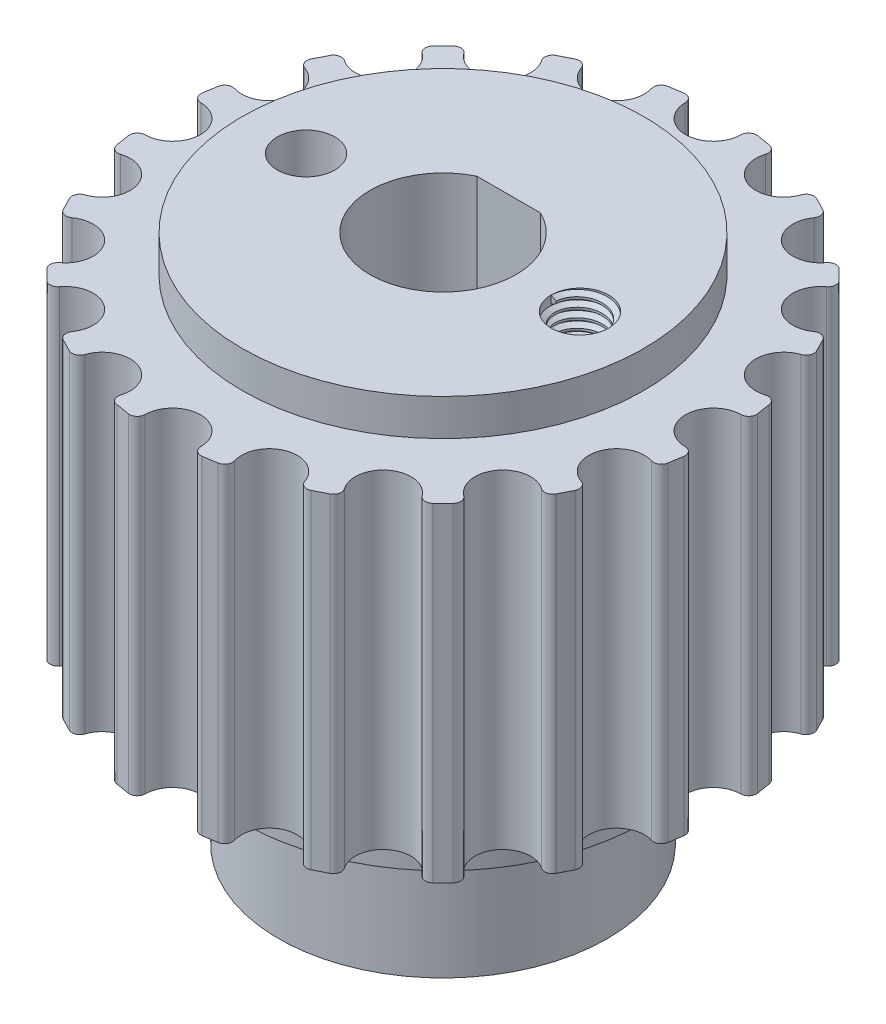
SolidWorks part; units mm, degrees
ref_plane "Ebene vorne" through (0, 0, 0) normal (0, 0, 1) x (1, 0, 0)
ref_plane "Ebene oben" through (0, 0, 0) normal (0, 1, 0) x (1, 0, 0)
ref_plane "Ebene rechts" through (0, 0, 0) normal (1, 0, 0) x (0, 0, -1)
sketch "Skizze1" plane through (0, 0, 0) normal (0, 1, 0) x (1, 0, 0)
  line L0 (0, 0) -> (0, 12990.3785) construction
  line L1 (0, 0) -> (-12990.3785, 0) construction
  line L2 (0, 0) -> (7.951, 24.4706) construction
  line L3 (2.7773, 15.0914) -> (2.0221, 15.211)
  line L4 (7.3049, 13.4946) -> (6.6236, 13.8417)
  line L5 (11.1174, 10.5768) -> (10.5768, 11.1174)
  line L6 (13.8417, 6.6236) -> (13.4946, 7.3049)
  line L7 (15.211, 2.0221) -> (15.0914, 2.7773)
  line L8 (15.0914, -2.7773) -> (15.211, -2.0221)
  line L9 (13.4946, -7.3049) -> (13.8417, -6.6236)
  line L10 (10.5768, -11.1174) -> (11.1174, -10.5768)
  line L11 (6.6236, -13.8417) -> (7.3049, -13.4946)
  line L12 (2.0221, -15.211) -> (2.7773, -15.0914)
  line L13 (-2.7773, -15.0914) -> (-2.0221, -15.211)
  line L14 (-7.3049, -13.4946) -> (-6.6236, -13.8417)
  line L15 (-11.1174, -10.5768) -> (-10.5768, -11.1174)
  line L16 (-13.8417, -6.6236) -> (-13.4946, -7.3049)
  line L17 (-15.211, -2.0221) -> (-15.0914, -2.7773)
  line L18 (-15.0914, 2.7773) -> (-15.211, 2.0221)
  line L19 (-13.4946, 7.3049) -> (-13.8417, 6.6236)
  line L20 (-10.5768, 11.1174) -> (-11.1174, 10.5768)
  line L21 (-6.6236, 13.8417) -> (-7.3049, 13.4946)
  line L22 (-2.0221, 15.211) -> (-2.7773, 15.0914)
  circle A0 centre (0, 0) radius 15.345 construction
  circle A1 centre (0, 0) radius 13.285 construction
  arc A2 (0, 13.285) -> (1.5249, 14.7915) centre (0, 14.81) ccw
  arc A3 (2.0221, 15.211) -> (1.5249, 14.7915) centre (1.9549, 14.7863) ccw
  arc A4 (3.1206, 14.5388) -> (4.1053, 12.6348) centre (4.5765, 14.0851) ccw
  arc A5 (3.1206, 14.5388) -> (2.7773, 15.0914) centre (2.7101, 14.6667) ccw
  arc A6 (4.1053, 12.6348) -> (6.0211, 13.5964) centre (4.5765, 14.0851) ccw
  arc A7 (6.6236, 13.8417) -> (6.0211, 13.5964) centre (6.4284, 13.4586) ccw
  arc A8 (7.4606, 12.8629) -> (7.3049, 13.4946) centre (7.1097, 13.1114) ccw
  arc A9 (7.4606, 12.8629) -> (7.8087, 10.7478) centre (8.7051, 11.9815) ccw
  arc A10 (7.8087, 10.7478) -> (9.9279, 11.0703) centre (8.7051, 11.9815) ccw
  arc A11 (10.5768, 11.1174) -> (9.9279, 11.0703) centre (10.2727, 10.8134) ccw
  arc A12 (11.0703, 9.9279) -> (11.1174, 10.5768) centre (10.8134, 10.2727) ccw
  arc A13 (11.0703, 9.9279) -> (10.7478, 7.8087) centre (11.9815, 8.7051) ccw
  arc A14 (10.7478, 7.8087) -> (12.8629, 7.4606) centre (11.9815, 8.7051) ccw
  arc A15 (13.4946, 7.3049) -> (12.8629, 7.4606) centre (13.1114, 7.1097) ccw
  arc A16 (13.5964, 6.0211) -> (13.8417, 6.6236) centre (13.4586, 6.4284) ccw
  arc A17 (13.5964, 6.0211) -> (12.6348, 4.1053) centre (14.0851, 4.5765) ccw
  arc A18 (12.6348, 4.1053) -> (14.5388, 3.1206) centre (14.0851, 4.5765) ccw
  arc A19 (15.0914, 2.7773) -> (14.5388, 3.1206) centre (14.6667, 2.7101) ccw
  arc A20 (14.7915, 1.5249) -> (15.211, 2.0221) centre (14.7863, 1.9549) ccw
  arc A21 (14.7915, 1.5249) -> (13.285, 0) centre (14.81, 0) ccw
  arc A22 (13.285, 0) -> (14.7915, -1.5249) centre (14.81, 0) ccw
  arc A23 (15.211, -2.0221) -> (14.7915, -1.5249) centre (14.7863, -1.9549) ccw
  arc A24 (14.5388, -3.1206) -> (15.0914, -2.7773) centre (14.6667, -2.7101) ccw
  arc A25 (14.5388, -3.1206) -> (12.6348, -4.1053) centre (14.0851, -4.5765) ccw
  arc A26 (12.6348, -4.1053) -> (13.5964, -6.0211) centre (14.0851, -4.5765) ccw
  arc A27 (13.8417, -6.6236) -> (13.5964, -6.0211) centre (13.4586, -6.4284) ccw
  arc A28 (12.8629, -7.4606) -> (13.4946, -7.3049) centre (13.1114, -7.1097) ccw
  arc A29 (12.8629, -7.4606) -> (10.7478, -7.8087) centre (11.9815, -8.7051) ccw
  arc A30 (10.7478, -7.8087) -> (11.0703, -9.9279) centre (11.9815, -8.7051) ccw
  arc A31 (11.1174, -10.5768) -> (11.0703, -9.9279) centre (10.8134, -10.2727) ccw
  arc A32 (9.9279, -11.0703) -> (10.5768, -11.1174) centre (10.2727, -10.8134) ccw
  arc A33 (9.9279, -11.0703) -> (7.8087, -10.7478) centre (8.7051, -11.9815) ccw
  arc A34 (7.8087, -10.7478) -> (7.4606, -12.8629) centre (8.7051, -11.9815) ccw
  arc A35 (7.3049, -13.4946) -> (7.4606, -12.8629) centre (7.1097, -13.1114) ccw
  arc A36 (6.0211, -13.5964) -> (6.6236, -13.8417) centre (6.4284, -13.4586) ccw
  arc A37 (6.0211, -13.5964) -> (4.1053, -12.6348) centre (4.5765, -14.0851) ccw
  arc A38 (4.1053, -12.6348) -> (3.1206, -14.5388) centre (4.5765, -14.0851) ccw
  arc A39 (2.7773, -15.0914) -> (3.1206, -14.5388) centre (2.7101, -14.6667) ccw
  arc A40 (1.5249, -14.7915) -> (2.0221, -15.211) centre (1.9549, -14.7863) ccw
  arc A41 (1.5249, -14.7915) -> (0, -13.285) centre (0, -14.81) ccw
  arc A42 (0, -13.285) -> (-1.5249, -14.7915) centre (0, -14.81) ccw
  arc A43 (-2.0221, -15.211) -> (-1.5249, -14.7915) centre (-1.9549, -14.7863) ccw
  arc A44 (-3.1206, -14.5388) -> (-2.7773, -15.0914) centre (-2.7101, -14.6667) ccw
  arc A45 (-3.1206, -14.5388) -> (-4.1053, -12.6348) centre (-4.5765, -14.0851) ccw
  arc A46 (-4.1053, -12.6348) -> (-6.0211, -13.5964) centre (-4.5765, -14.0851) ccw
  arc A47 (-6.6236, -13.8417) -> (-6.0211, -13.5964) centre (-6.4284, -13.4586) ccw
  arc A48 (-7.4606, -12.8629) -> (-7.3049, -13.4946) centre (-7.1097, -13.1114) ccw
  arc A49 (-7.4606, -12.8629) -> (-7.8087, -10.7478) centre (-8.7051, -11.9815) ccw
  arc A50 (-7.8087, -10.7478) -> (-9.9279, -11.0703) centre (-8.7051, -11.9815) ccw
  arc A51 (-10.5768, -11.1174) -> (-9.9279, -11.0703) centre (-10.2727, -10.8134) ccw
  arc A52 (-11.0703, -9.9279) -> (-11.1174, -10.5768) centre (-10.8134, -10.2727) ccw
  arc A53 (-11.0703, -9.9279) -> (-10.7478, -7.8087) centre (-11.9815, -8.7051) ccw
  arc A54 (-10.7478, -7.8087) -> (-12.8629, -7.4606) centre (-11.9815, -8.7051) ccw
  arc A55 (-13.4946, -7.3049) -> (-12.8629, -7.4606) centre (-13.1114, -7.1097) ccw
  arc A56 (-13.5964, -6.0211) -> (-13.8417, -6.6236) centre (-13.4586, -6.4284) ccw
  arc A57 (-13.5964, -6.0211) -> (-12.6348, -4.1053) centre (-14.0851, -4.5765) ccw
  arc A58 (-12.6348, -4.1053) -> (-14.5388, -3.1206) centre (-14.0851, -4.5765) ccw
  arc A59 (-15.0914, -2.7773) -> (-14.5388, -3.1206) centre (-14.6667, -2.7101) ccw
  arc A60 (-14.7915, -1.5249) -> (-15.211, -2.0221) centre (-14.7863, -1.9549) ccw
  arc A61 (-14.7915, -1.5249) -> (-13.285, 0) centre (-14.81, 0) ccw
  arc A62 (-13.285, 0) -> (-14.7915, 1.5249) centre (-14.81, 0) ccw
  arc A63 (-15.211, 2.0221) -> (-14.7915, 1.5249) centre (-14.7863, 1.9549) ccw
  arc A64 (-14.5388, 3.1206) -> (-15.0914, 2.7773) centre (-14.6667, 2.7101) ccw
  arc A65 (-14.5388, 3.1206) -> (-12.6348, 4.1053) centre (-14.0851, 4.5765) ccw
  arc A66 (-12.6348, 4.1053) -> (-13.5964, 6.0211) centre (-14.0851, 4.5765) ccw
  arc A67 (-13.8417, 6.6236) -> (-13.5964, 6.0211) centre (-13.4586, 6.4284) ccw
  arc A68 (-12.8629, 7.4606) -> (-13.4946, 7.3049) centre (-13.1114, 7.1097) ccw
  arc A69 (-12.8629, 7.4606) -> (-10.7478, 7.8087) centre (-11.9815, 8.7051) ccw
  arc A70 (-10.7478, 7.8087) -> (-11.0703, 9.9279) centre (-11.9815, 8.7051) ccw
  arc A71 (-11.1174, 10.5768) -> (-11.0703, 9.9279) centre (-10.8134, 10.2727) ccw
  arc A72 (-9.9279, 11.0703) -> (-10.5768, 11.1174) centre (-10.2727, 10.8134) ccw
  arc A73 (-9.9279, 11.0703) -> (-7.8087, 10.7478) centre (-8.7051, 11.9815) ccw
  arc A74 (-7.8087, 10.7478) -> (-7.4606, 12.8629) centre (-8.7051, 11.9815) ccw
  arc A75 (-7.3049, 13.4946) -> (-7.4606, 12.8629) centre (-7.1097, 13.1114) ccw
  arc A76 (-6.0211, 13.5964) -> (-6.6236, 13.8417) centre (-6.4284, 13.4586) ccw
  arc A77 (-6.0211, 13.5964) -> (-4.1053, 12.6348) centre (-4.5765, 14.0851) ccw
  arc A78 (-4.1053, 12.6348) -> (-3.1206, 14.5388) centre (-4.5765, 14.0851) ccw
  arc A79 (-2.7773, 15.0914) -> (-3.1206, 14.5388) centre (-2.7101, 14.6667) ccw
  arc A80 (-1.5249, 14.7915) -> (-2.0221, 15.211) centre (-1.9549, 14.7863) ccw
  arc A81 (-1.5249, 14.7915) -> (0, 13.285) centre (0, 14.81) ccw
  point P212 (0, 0)
  dimension "D1" = 30.69
  dimension "D2" = 26.57
  dimension "D3" = 3.05
  dimension "D4" = 0.86
  dimension "D5" = 18
  dimension "D6" = 20
extrude "Aufsatz-Linear austragen1" add sketch "Skizze1" along normal blind 18
sketch "Skizze4" plane through (0, 0, 0) normal (0, 0, 1) x (1, 0, 0)
  line L0 (0, -1014) -> (0, -7) construction
  line L2 (11, 0) -> (11, -2.5)
  line L3 (7.1801, 0) -> (9.9279, 0) construction
  line L4 (11, -2.5) -> (9, -2.5)
  line L5 (9, -2.5) -> (9, -9)
  line L6 (9, -9) -> (0, -9)
  line L8 (0, 0) -> (11, 0)
  line L9 (0, -9) -> (0, 0)
  line L10 (0, 0) -> (0, 50000) construction
  point P11 (11, -1.25)
  dimension "D1" = 18
  dimension "D2" = 22
  dimension "D3" = 6.5
  dimension "D4" = 2.5
revolve "Rotation1" add sketch "Skizze4" angle 360 about L0
sketch "Skizze8" plane through (0, 18, 0) normal (0, 1, 0) x (1, 0, 0)
  circle A0 centre (0, 0) radius 11
  dimension "D1" = 22
extrude "Aufsatz-Linear austragen3" add sketch "Skizze8" along normal blind 2
sketch "Skizze7" plane through (0, 18, 0) normal (0, 1, 0) x (1, 0, 0)
  line L0 (0, -4) -> (0, 3.6) construction
  line L1 (0, -15.95) -> (0, 15.95) construction
  line L2 (-1.7436, 3.6) -> (1.7436, 3.6)
  arc A0 (-1.7436, 3.6) -> (1.7436, 3.6) centre (0, 0) ccw
  dimension "D2" = 8
  dimension "D1" = 7.6
extrude "Schnitt-Linear austragen3" cut sketch "Skizze7" against normal through all both and the other way through all
hole_wizard "Gewindebohrung für M3x0.5 Helicoil1" positions "Skizze9" profile "Skizze10" tap size "M3x0.5" standard "Helicoil® Metric"
sketch "Skizze9" plane through (0, 20, 0) normal (0, 1, 0) x (1, 0, 0)
  line L0 (-15.95, 0) -> (15.95, 0) construction
  line L1 (0, 0) -> (0, 50000) construction
  point P0 (7.5, 0)
  point P4 (-7.5, 0)
  dimension "D1" = 15
sketch "Skizze10" plane through (7.5, 20, 0) normal (1, 0, 0) x (0, 0, 1)
  line L0 (0, 0) -> (0, 7.5)
  line L1 (0, 7.5) -> (1.575, 6.5536)
  line L2 (1.575, 6.5536) -> (1.575, 0)
  line L5 (1.575, 0) -> (0, 0)
  line L10 (0, 7.5) -> (-1.575, 6.5536) construction
  line L11 (0, -6.35) -> (0, 107.95) construction
  dimension "Bohrerdurchmesser" = 3.15
  dimension "Bohrungstiefe" = 7.5
  dimension "Spitzenwinkel" = 118
cosmetic thread "Bohrungsgewinde1" parameters "D1"=3.5, "D2"=3.716
cosmetic thread "Bohrungsgewinde2" parameters "D1"=3.5, "D2"=3.716
thread "Gewinde1" pitch 0.5 method extrude profile "Gewindeprofil1" start angle 0, offset 0, length 10, pitch 0.5, diameter 3.15
ref_plane "Ebene1" through (5.925, 20, 0) normal (0, 0, 1) x (-1, 0, 0)
sketch "Gewindeprofil1" plane through (5.925, 20, 0) normal (0, 0, 1) x (-1, 0, 0)
  line L0 (0, 0) -> (0, 0.5) construction
  line L11 (0, 0) -> (0, 0.4375)
  line L12 (0, 0.4375) -> (-0.2706, 0.2812)
  line L13 (-0.2706, 0.2812) -> (-0.2706, 0.1562)
  line L15 (-0.2706, 0.1562) -> (0, 0)
  line L17 (-0.2706, 0.2187) -> (0, 0.2187) construction
  point P2 (0, 0)
  dimension "Pitch" = 0.5
  dimension "Profile_Angle" = 60
  dimension "Profile_Land" = 0.125
  dimension "Profile_Height" = 0.2706
sketch "Skizze6" plane through (0, 0, 0) normal (0, 0, 1) x (1, 0, 0)
  line L0 (-0.3514, -9) -> (0.6486, -9)
  line L1 (-9, -9) -> (9, -9) construction
  line L2 (0.6486, -9) -> (0.6486, -2.5)
  line L3 (-9, -2.5) -> (9, -2.5) construction
  line L4 (0.6486, -2.5) -> (-0.3514, -2.5)
  line L5 (-0.3514, -2.5) -> (-0.3514, -9)
  dimension "D1" = 1
